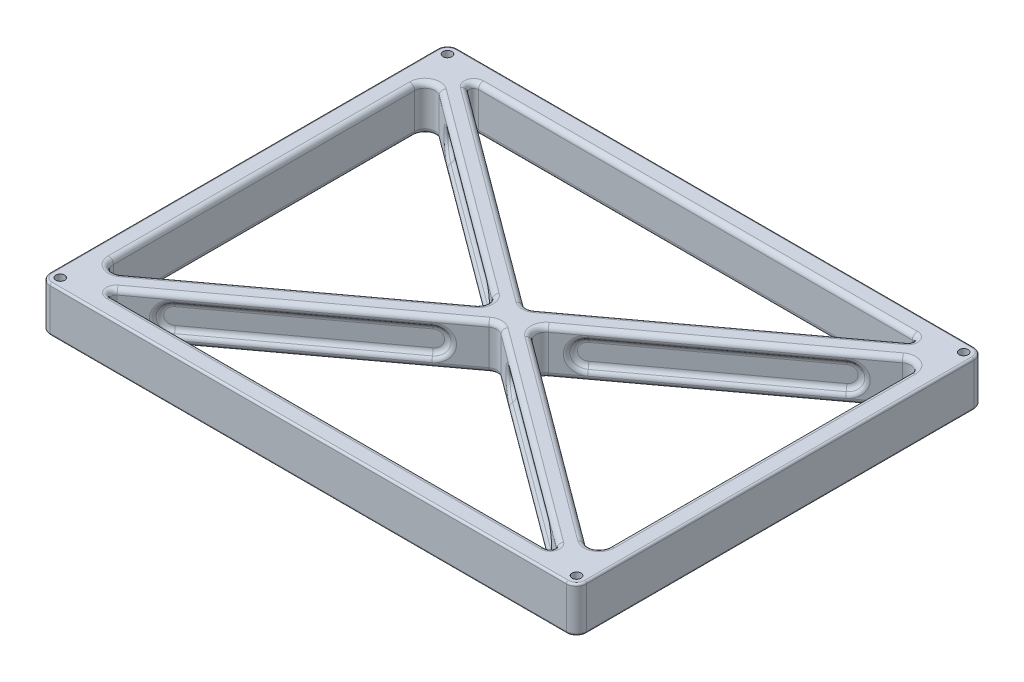
SolidWorks part; units mm, degrees
ref_plane "Front Plane" through (0, 0, 0) normal (0, 0, 1) x (1, 0, 0)
ref_plane "Top Plane" through (0, 0, 0) normal (0, 1, 0) x (1, 0, 0)
ref_plane "Right Plane" through (0, 0, 0) normal (1, 0, 0) x (0, 0, -1)
sketch "Sketch1" plane through (0, 0, 0) normal (0, 1, 0) x (1, 0, 0)
  line L0 (-122, 84.0306) -> (113.5926, -90.25)
  line L1 (127, -95.25) -> (-127, -95.25) construction
  line L2 (127, -95.25) -> (127, 95.25) construction
  line L3 (127, 95.25) -> (-127, 95.25) construction
  line L4 (-127, -95.25) -> (-127, 95.25) construction
  line L5 (127, -95.25) -> (-127, 95.25) construction
  line L6 (127, 95.25) -> (-127, -95.25) construction
  line L7 (132, -100.25) -> (-132, -100.25)
  line L8 (132, -100.25) -> (132, 100.25)
  line L9 (132, 100.25) -> (-132, 100.25)
  line L10 (-132, -100.25) -> (-132, 100.25)
  line L11 (132, -100.25) -> (-132, 100.25) construction
  line L12 (132, 100.25) -> (-132, -100.25) construction
  line L13 (122, -90.25) -> (-122, -90.25)
  line L14 (122, -90.25) -> (122, 90.25)
  line L15 (122, 90.25) -> (-122, 90.25)
  line L16 (-122, -90.25) -> (-122, 90.25)
  line L17 (122, -90.25) -> (-122, 90.25) construction
  line L18 (122, 90.25) -> (-122, -90.25) construction
  line L19 (122, -84.0306) -> (-113.5926, 90.25)
  line L20 (-113.5926, -90.25) -> (122, 84.0306)
  line L21 (113.5926, 90.25) -> (-122, -84.0306)
  circle A0 centre (-127, -95.25) radius 2.2
  circle A1 centre (127, -95.25) radius 2.2
  circle A2 centre (127, 95.25) radius 2.2
  circle A3 centre (-127, 95.25) radius 2.2
  point P0 (0, 0)
  point P10 (0, 0)
  point P15 (0, 0)
  dimension "D3" = 4.4
  dimension "D4" = 10
  dimension "D1" = 254
  dimension "D2" = 190.5
  dimension "D5" = 10
  dimension "D6" = 10
  dimension "D7" = 10
extrude "Boss-Extrude1" add sketch "Sketch1" along normal blind 22.2504 contours L10 L7 L8 L9 A3 A2 A1 A0 L13 L16 L15 L14 | L21 L19 L15 L16 L0 | L20 L0 L13 L14 L19 | L0 L21 L16 L13 L20 | L15 L21 L19 L20 L14 | L19 L21 L0 L20 region at (-62.0573, 0, -45.9071) region at (0, 0, 0) region at (-62.0573, 0, 45.9071) region at (62.0573, 0, 45.9071) region at (62.0573, 0, -45.9071) region at (0, 0, 96.9349)
fillet "Fillet1" radius 5 12 edges at (8.4074, 11.1252, 0) (0, 11.1252, 6.2194) (-8.4074, 11.1252, 0) (0, 11.1252, -6.2194) (122, 11.1252, 84.0306) (-122, 11.1252, 84.0306) (122, 11.1252, -84.0306) (-122, 11.1252, -84.0306) (-132, 11.1252, -100.25) (132, 11.1252, -100.25) (132, 11.1252, 100.25) (-132, 11.1252, 100.25)
fillet "Fillet2" radius 1 16 edges at (130.5355, 0, 98.7855) (132, 0, 0) (130.5355, 0, -98.7855) (0, 0, -100.25) (-130.5355, 0, -98.7855) (-132, 0, 0) (-130.5355, 0, 98.7855) (-130.5355, 22.2504, 98.7855) (0, 22.2504, 100.25) (130.5355, 22.2504, 98.7855) (132, 22.2504, 0) (130.5355, 22.2504, -98.7855) (0, 22.2504, -100.25) (-130.5355, 22.2504, -98.7855) (0, 0, 100.25) (-132, 22.2504, 0)
fillet "Fillet4" radius 2.25 4 edges at (113.5926, 11.1252, 90.25) (-113.5926, 11.1252, 90.25) (113.5926, 11.1252, -90.25) (-113.5926, 11.1252, -90.25)
fillet "Fillet3" radius 2.5 48 edges at (55.5397, 0, -47.3051) (0, 0, -7.4388) (-55.5397, 0, -47.3051) (0, 22.2504, -90.25) (-55.5397, 22.2504, -47.3051) (0, 22.2504, -7.4388) (11.8148, 0, 0) (63.9338, 0, 41.0759) (119.2508, 0, 78.5772) (122, 0, 0) (119.2508, 0, -78.5772) (11.8148, 22.2504, 0) (63.9338, 22.2504, 41.0759) (119.2508, 22.2504, 78.5772) (122, 22.2504, 0) (119.2508, 22.2504, -78.5772) (0, 22.2504, 7.4388) (-55.5397, 22.2504, 47.3051) (0, 22.2504, 90.25) (0, 0, 90.25) (55.5397, 0, 47.3051) (0, 0, 7.4388) (-119.2508, 0, 78.5772) (-63.9338, 0, 41.0759) (-11.8148, 0, 0) (-63.9338, 0, -41.0759) (-119.2508, 0, -78.5772) (-119.2508, 22.2504, 78.5772) (-63.9338, 22.2504, 41.0759) (-11.8148, 22.2504, 0) (-63.9338, 22.2504, -41.0759) (-119.2508, 22.2504, -78.5772) (0, 0, -90.25) (55.5397, 22.2504, -47.3051) (63.9338, 0, -41.0759) (63.9338, 22.2504, -41.0759) (55.5397, 22.2504, 47.3051) (-55.5397, 0, 47.3051) (-122, 0, 0) (-122, 22.2504, 0) (108.9046, 0, -88.7045) (-108.9046, 0, -88.7045) (108.9046, 22.2504, -88.7045) (-108.9046, 22.2504, -88.7045) (-108.9046, 22.2504, 88.7045) (108.9046, 22.2504, 88.7045) (-108.9046, 0, 88.7045) (108.9046, 0, 88.7045)
sketch "Sketch3" plane through (-2.9736, 0, 4.0197) normal (-0.5947, 0, 0.8039) x (0.8039, 0, 0.5947)
  line L0 (-138.1364, 19.7504) -> (-138.1364, 2.5) construction
  line L1 (-138.1364, 19.7504) -> (-138.1364, 2.5)
  line L2 (-138.1364, 11.1252) -> (-126.0375, 11.1252) construction
  line L3 (-118.1364, 11.1252) -> (-27.3975, 11.1252) construction
  line L4 (-118.1364, 17.2504) -> (-27.3975, 17.2504)
  line L5 (-118.1364, 5) -> (-27.3975, 5)
  line L6 (-13.518, 19.7504) -> (-138.1364, 19.7504) construction
  line L8 (27.3975, 11.1252) -> (118.1694, 11.1252) construction
  line L9 (27.3975, 17.2504) -> (118.1694, 17.2504)
  line L10 (27.3975, 5) -> (118.1694, 5)
  line L11 (138.1694, 19.7504) -> (7.3975, 19.7504) construction
  line L12 (7.3975, 19.7504) -> (7.3975, 2.5) construction
  line L13 (138.1694, 2.5) -> (138.1694, 19.7504) construction
  line L14 (-7.3975, 19.7504) -> (-7.3975, 2.5) construction
  arc A0 (-118.1364, 17.2504) -> (-118.1364, 5) centre (-118.1364, 11.1252) ccw
  arc A1 (-27.3975, 5) -> (-27.3975, 17.2504) centre (-27.3975, 11.1252) ccw
  arc A2 (27.3975, 17.2504) -> (27.3975, 5) centre (27.3975, 11.1252) ccw
  arc A3 (118.1694, 5) -> (118.1694, 17.2504) centre (118.1694, 11.1252) ccw
  point P2 (-138.1364, 11.1252)
  point P7 (-72.7669, 11.1252)
  point P18 (72.7835, 11.1252)
  dimension "D1" = 2.5
  dimension "D2" = 20
  dimension "D3" = 20
  dimension "D4" = 2.5
  dimension "D5" = 20
  dimension "D6" = 20
extrude "Cut-Extrude3" cut sketch "Sketch3" against normal blind 2.5 contours L5 A1 L4 A0 | L10 A3 L9 A2 region at (-61.4736, 11.1252, -39.2559) region at (55.5397, 11.1252, 47.3051)
extrude "Cut-Extrude4" cut sketch "Sketch3<3>" along normal blind 2.5 from surface contours L5 A1 L4 A0 | L10 A3 L9 A2 region at (-61.4736, 11.1252, -39.2559) region at (55.5397, 11.1252, 47.3051) starting at face at (63.9338, 11.1252, 41.0759)
sketch "Sketch3<3>" plane through (-2.9736, 0, 4.0197) normal (-0.5947, 0, 0.8039) x (0.8039, 0, 0.5947) same geometry as "Sketch3"
sketch "Sketch4" plane through (-2.9736, 0, -4.0197) normal (-0.5947, 0, -0.8039) x (-0.8039, 0, 0.5947)
  line L0 (-7.3975, 2.5) -> (-7.3975, 19.7504) construction
  line L1 (-7.3975, 2.5) -> (-7.3975, 19.7504)
  line L2 (-7.3975, 11.1252) -> (-56.379, 11.1252) construction
  line L3 (-27.3975, 11.1252) -> (-118.1694, 11.1252) construction
  line L4 (-27.3975, 5) -> (-118.1694, 5)
  line L5 (-27.3975, 17.2504) -> (-118.1694, 17.2504)
  line L6 (-138.1694, 19.7504) -> (-138.1694, 2.5) construction
  line L7 (-7.3975, 19.7504) -> (-138.1694, 19.7504) construction
  line L8 (27.3975, 11.1252) -> (118.1364, 11.1252) construction
  line L9 (27.3975, 17.2504) -> (118.1364, 17.2504)
  line L10 (27.3975, 5) -> (118.1364, 5)
  line L12 (138.1364, 2.5) -> (138.1364, 19.7504) construction
  line L13 (138.1364, 19.7504) -> (13.518, 19.7504) construction
  line L15 (7.3975, 2.5) -> (7.3975, 19.7504) construction
  arc A0 (-27.3975, 5) -> (-27.3975, 17.2504) centre (-27.3975, 11.1252) ccw
  arc A1 (-118.1694, 17.2504) -> (-118.1694, 5) centre (-118.1694, 11.1252) ccw
  arc A2 (27.3975, 17.2504) -> (27.3975, 5) centre (27.3975, 11.1252) ccw
  arc A3 (118.1364, 5) -> (118.1364, 17.2504) centre (118.1364, 11.1252) ccw
  point P2 (-7.3975, 11.1252)
  point P7 (-72.7835, 11.1252)
  point P18 (72.7669, 11.1252)
  dimension "D1" = 20
  dimension "D2" = 20
  dimension "D3" = 2.5
  dimension "D4" = 20
  dimension "D5" = 20
  dimension "D6" = 2.5
extrude "Cut-Extrude5" cut sketch "Sketch4" against normal blind 2.5 contours L5 A1 L4 A0 | L10 A3 L9 A2 region at (55.5397, 11.1252, -47.3051) region at (-61.4736, 11.1252, 39.2559)
extrude "Cut-Extrude6" cut sketch "Sketch4<3>" along normal blind 2.5 from surface contours L5 A1 L4 A0 | L10 A3 L9 A2 region at (55.5397, 11.1252, -47.3051) region at (-61.4736, 11.1252, 39.2559) starting at face at (-55.5397, 11.1252, 47.3051)
sketch "Sketch4<3>" plane through (-2.9736, 0, -4.0197) normal (-0.5947, 0, -0.8039) x (-0.8039, 0, 0.5947) same geometry as "Sketch4"
fillet "Fillet6" radius 2.5 32 edges at (-55.5264, 17.2504, 47.2953) (-96.9248, 11.1252, 77.9199) (-55.5264, 5, 47.2953) (55.5397, 17.2504, 47.3051) (96.9514, 11.1252, 77.9396) (55.5397, 5, 47.3051) (-61.4736, 17.2504, 39.2559) (-102.872, 11.1252, 69.8806) (-61.4736, 5, 39.2559) (-61.4736, 5, -39.2559) (-102.872, 11.1252, -69.8806) (-61.4736, 17.2504, -39.2559) (-55.5264, 5, -47.2953) (-96.9248, 11.1252, -77.9199) (-55.5264, 17.2504, -47.2953) (61.4869, 5, -39.2658) (102.8985, 11.1252, -69.9002) (61.4869, 17.2504, -39.2658) (55.5397, 5, -47.3051) (96.9514, 11.1252, -77.9396) (55.5397, 17.2504, -47.3051) (20.0752, 11.1252, 8.6313) (61.4869, 5, 39.2658) (102.8985, 11.1252, 69.9002) (-14.128, 11.1252, 16.6707) (14.128, 11.1252, 16.6707) (-20.0752, 11.1252, 8.6313) (-20.0752, 11.1252, -8.6313) (-14.128, 11.1252, -16.6707) (20.0752, 11.1252, -8.6313) (14.128, 11.1252, -16.6707) (61.4869, 17.2504, 39.2658)
fillet "Fillet7" radius 3 32 edges at (-98.4116, 11.1252, -75.9101) (-57.0132, 17.2504, -45.2855) (-15.6148, 11.1252, -14.6608) (-59.9868, 17.2504, -41.2658) (-18.5884, 11.1252, -10.6411) (-59.9868, 5, -41.2658) (-59.9868, 17.2504, 41.2658) (-101.3852, 11.1252, 71.8904) (-59.9868, 5, 41.2658) (-57.0132, 17.2504, 45.2855) (-98.4116, 11.1252, 75.9101) (-57.0132, 5, 45.2855) (60.0001, 17.2504, 41.2756) (101.4118, 11.1252, 71.9101) (60.0001, 5, 41.2756) (57.0265, 17.2504, 45.2953) (98.4382, 11.1252, 75.9297) (57.0265, 5, 45.2953) (60.0001, 17.2504, -41.2756) (18.5884, 11.1252, -10.6411) (60.0001, 5, -41.2756) (57.0265, 17.2504, -45.2953) (15.6148, 11.1252, -14.6608) (57.0265, 5, -45.2953) (-57.0132, 5, -45.2855) (-101.3852, 11.1252, -71.8904) (-18.5884, 11.1252, 10.6411) (-15.6148, 11.1252, 14.6608) (18.5884, 11.1252, 10.6411) (15.6148, 11.1252, 14.6608) (101.4118, 11.1252, -71.9101) (98.4382, 11.1252, -75.9297)
